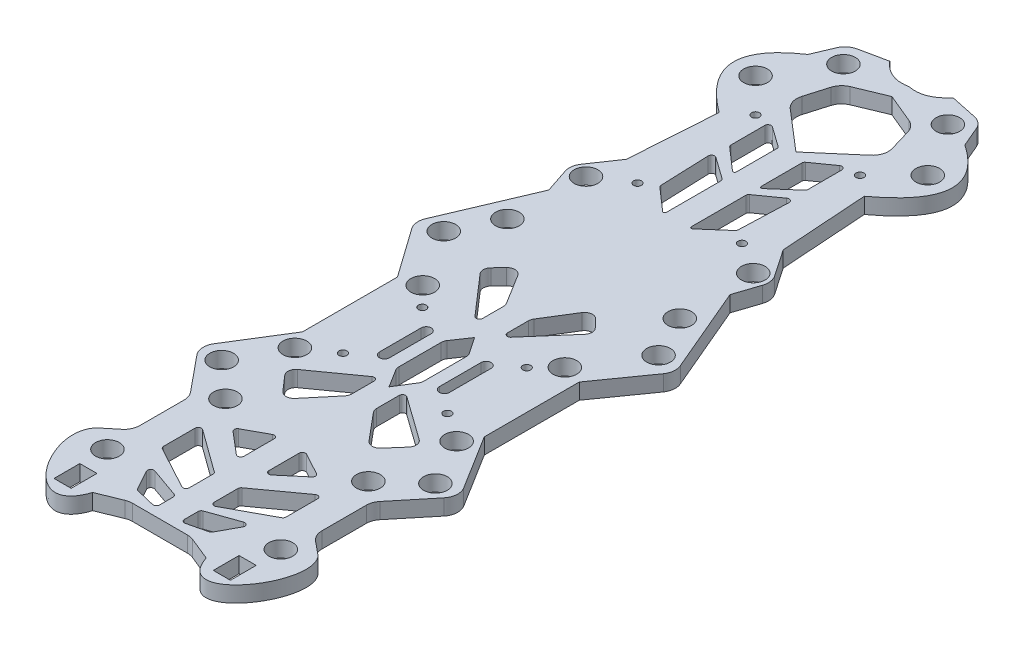
SolidWorks part; units mm, degrees
ref_plane "Front Plane" through (0, 0, 0) normal (0, 0, 1) x (1, 0, 0)
ref_plane "Top Plane" through (0, 0, 0) normal (0, 1, 0) x (1, 0, 0)
ref_plane "Right Plane" through (0, 0, 0) normal (1, 0, 0) x (0, 0, -1)
sketch "Sketch1" plane through (0, 0, 0) normal (0, 1, 0) x (1, 0, 0)
  line L0 (0, -362.1427) -> (0, 100.8573) construction
  line L1 (-20, 108.6669) -> (-37.0216, 105.0994)
  line L2 (-44.1736, 99.2235) -> (-49.5631, 86.5422)
  line L3 (-45.8473, 26.7499) -> (-49.5631, -28.2501)
  line L4 (-49.5631, -28.2501) -> (-61.1711, -45.2719)
  line L5 (-62.3986, -54.0608) -> (-57.2521, -69.541)
  line L6 (-57.2521, -69.541) -> (-80.4938, -124.2273)
  line L7 (-79.4523, -133.9167) -> (-57.4483, -164.9992)
  line L8 (-57.4483, -164.9992) -> (-57.4483, -224.9992)
  line L9 (-57.4483, -224.9992) -> (-78.8878, -259.4412)
  line L10 (-78.1289, -271.0691) -> (-59.8267, -293.374)
  line L11 (-57.5574, -299.7173) -> (-57.5574, -327.686)
  line L12 (-61.214, -335.4166) -> (-70.1168, -342.7217)
  line L13 (-35.8433, -379.1849) -> (-21.2763, -373.2441)
  line L14 (-17.5, -372.5037) -> (17.5, -372.5037)
  line L15 (0, -362.1427) -> (0, -406.857) construction
  line L16 (35.8433, -379.1849) -> (21.2763, -373.2441)
  line L17 (61.214, -335.4166) -> (70.1168, -342.7217)
  line L18 (57.5574, -299.7173) -> (57.5574, -327.686)
  line L19 (78.1289, -271.0691) -> (59.8267, -293.374)
  line L20 (57.4483, -224.9992) -> (78.8878, -259.4412)
  line L21 (57.4483, -164.9992) -> (57.4483, -224.9992)
  line L22 (79.4523, -133.9167) -> (57.4483, -164.9992)
  line L23 (57.2521, -69.541) -> (80.4938, -124.2273)
  line L24 (62.3986, -54.0608) -> (57.2521, -69.541)
  line L25 (49.5631, -28.2501) -> (61.1711, -45.2719)
  line L26 (45.8473, 26.7499) -> (49.5631, -28.2501)
  line L27 (44.1736, 99.2235) -> (49.5631, 86.5422)
  line L28 (20, 108.6669) -> (37.0216, 105.0994)
  line L29 (-82.7668, -406.857) -> (-82.7668, 285.8129) construction
  line L30 (-88.9889, 108.6669) -> (83.0349, 108.6669) construction
  line L31 (83.0349, 108.6669) -> (83.0349, -390.8771) construction
  line L32 (83.0349, -390.8771) -> (-226.8519, -390.8771) construction
  arc A0 (-17.5, -372.5037) -> (-21.2763, -373.2441) centre (-17.5, -382.5037) ccw
  arc A1 (-78.8878, -259.4412) -> (-78.1289, -271.0691) centre (-70.3983, -264.7258) ccw
  arc A2 (-80.4938, -124.2273) -> (-79.4523, -133.9167) centre (-71.2905, -128.1387) ccw
  arc A3 (-61.1711, -45.2719) -> (-62.3986, -54.0608) centre (-52.9093, -50.906) ccw
  arc A4 (-57.5574, -327.686) -> (-61.214, -335.4166) centre (-67.5574, -327.686) cw
  arc A5 (-57.5574, -299.7173) -> (-59.8267, -293.374) centre (-67.5574, -299.7173) ccw
  arc A6 (-44.1736, 99.2235) -> (-37.0216, 105.0994) centre (-34.9703, 95.3121) cw
  arc A7 (44.1736, 99.2235) -> (37.0216, 105.0994) centre (34.9703, 95.3121) ccw
  arc A8 (57.5574, -299.7173) -> (59.8267, -293.374) centre (67.5574, -299.7173) cw
  arc A9 (57.5574, -327.686) -> (61.214, -335.4166) centre (67.5574, -327.686) ccw
  arc A10 (61.1711, -45.2719) -> (62.3986, -54.0608) centre (52.9093, -50.906) cw
  arc A11 (80.4938, -124.2273) -> (79.4523, -133.9167) centre (71.2905, -128.1387) cw
  arc A12 (78.8878, -259.4412) -> (78.1289, -271.0691) centre (70.3983, -264.7258) cw
  arc A13 (17.5, -372.5037) -> (21.2763, -373.2441) centre (17.5, -382.5037) cw
  spline S0 degree 2 poles (0, 100.8573) (-11.4436, 98.5058) (-20, 108.6669) knots 0 0 0 1 1 1
  spline S1 degree 2 poles (-49.5631, 86.5422) (-90.2617, 59.181) (-45.8473, 26.7499) knots 0 0 0 1 1 1
  spline S2 degree 3 poles (-70.1168, -342.7217) (-85.3808, -360.6179) (-47.7027, -414.7904) (-35.8433, -379.1849) knots 0 0 0 0 1 1 1 1
  spline S3 degree 3 poles (70.1168, -342.7217) (85.3808, -360.6179) (47.7027, -414.7904) (35.8433, -379.1849) knots 0 0 0 0 1 1 1 1
  spline S4 degree 2 poles (49.5631, 86.5422) (90.2617, 59.181) (45.8473, 26.7499) knots 0 0 0 1 1 1
  spline S5 degree 2 poles (0, 100.8573) (11.4436, 98.5058) (20, 108.6669) knots 0 0 0 1 1 1
  point P28 (-82.6763, -129.3625)
  point P40 (-42.1315, 104.0285)
  point P74 (0, -372.5037)
  point P78 (42.1315, 104.0285)
  point P81 (81.2332, -129.2074)
  dimension "D2" = 60
  dimension "D3" = 19
  dimension "D4" = 65
  dimension "D6" = 10
  dimension "D7" = 10
  dimension "D8" = 10
  dimension "D9" = 10
  dimension "D10" = 10
  dimension "D11" = 10
  dimension "D12" = 10
  dimension "D5" = 55
  dimension "D13" = 40
  dimension "D14" = 35
  dimension "D15" = 499.544
  dimension "D16" = 165.8017
extrude "Boss-Extrude1" add sketch "Sketch1" along normal blind 10
sketch "Sketch2" plane through (0, 10, 0) normal (0, 1, 0) x (1, 0, 0)
  line L0 (0, 173.7032) -> (0, -467.5162) construction
  line L1 (0, 173.7032) -> (-7.8747, 173.7032) construction
  line L2 (0, 90.0147) -> (-18.6138, 82.2586)
  line L3 (-24.3598, 75.8542) -> (-28.5453, 61.6491)
  line L4 (-25.4693, 51.2374) -> (0, 29.3578)
  line L5 (-7.8747, 173.7032) -> (-7.8747, -465.9658) construction
  line L6 (-8.7157, 26.8032) -> (-21.2008, 35.6817)
  line L7 (-24.3598, 34.0518) -> (-24.3598, 12.6844)
  line L8 (-23.677, 11.1794) -> (-9.5333, -1.1996)
  line L9 (-7.8747, -0.4471) -> (-7.8747, 25.1733)
  line L10 (-8.7157, -8.572) -> (-22.3927, 1.1541)
  line L11 (-25.5504, -0.5507) -> (-24.3921, -31.4898)
  line L12 (-23.7107, -32.92) -> (-9.5333, -45.3284)
  line L13 (-7.8747, -44.5759) -> (-7.8747, -10.2019)
  line L14 (-28.1467, -125.3281) -> (-32.9558, -130.3865)
  line L15 (-33.1054, -137.1123) -> (-11.384, -162.0951)
  line L16 (-7.8747, -160.7828) -> (-7.8747, -147.5558)
  line L17 (-8.6255, -144.9206) -> (-20.2738, -126.138)
  line L18 (0, -173.7386) -> (-7.0144, -184.0936)
  line L19 (-7.8747, -186.8978) -> (-7.8747, -213.6766)
  line L20 (-7.1239, -216.3118) -> (0, -227.7989)
  line L21 (-18.953, -185.3637) -> (-18.953, -211.6699) construction
  line L24 (-15.7584, -185.3637) -> (-15.7584, -211.6699)
  line L25 (-22.1476, -185.3637) -> (-22.1476, -211.6699)
  line L26 (-7.8747, -229.1737) -> (-7.8747, -243.4693)
  line L27 (-9.0405, -246.6785) -> (-23.377, -263.8075)
  line L28 (-30.9765, -263.8881) -> (-39.2293, -254.4426)
  line L29 (-38.3716, -247.0851) -> (-11.0378, -227.5466)
  line L30 (-10.8337, -290.6718) -> (-24.5718, -298.1783)
  line L31 (-24.9054, -301.4595) -> (-11.1673, -313.0946)
  line L32 (-7.8747, -311.5684) -> (-7.8747, -292.4269)
  line L33 (-35.5342, -310.0309) -> (-8.7007, -329.4873)
  line L34 (-7.8747, -331.1065) -> (-7.8747, -346.0976)
  line L35 (-10.8266, -347.8565) -> (-37.66, -333.3358)
  line L36 (-38.7082, -331.5768) -> (-38.7082, -311.65)
  line L37 (-10.3394, -366.8465) -> (-22.4271, -363.9593)
  line L38 (-23.7176, -362.973) -> (-30.4958, -350.5676)
  line L39 (-28.0739, -347.7231) -> (-9.2079, -354.395)
  line L40 (-7.8747, -356.2806) -> (-7.8747, -364.9012)
  line L41 (7.1239, -216.3118) -> (0, -227.7989)
  line L42 (-55.7325, -367.4351) -> (-44.9064, -367.4351)
  line L43 (-55.7325, -367.4351) -> (-55.7325, -383.7424)
  line L44 (-55.7325, -383.7424) -> (-44.9064, -383.7424)
  line L45 (-44.9064, -367.4351) -> (-44.9064, -383.7424)
  line L46 (0, -173.7386) -> (7.0144, -184.0936)
  line L47 (25.4693, 51.2374) -> (0, 29.3578)
  line L48 (0, 90.0147) -> (18.6138, 82.2586)
  line L49 (18.953, -185.3637) -> (18.953, -211.6699) construction
  line L50 (15.7584, -185.3637) -> (15.7584, -211.6699)
  line L51 (22.1476, -185.3637) -> (22.1476, -211.6699)
  line L52 (44.9064, -367.4351) -> (44.9064, -383.7424)
  line L53 (55.7325, -383.7424) -> (44.9064, -383.7424)
  line L54 (55.7325, -367.4351) -> (55.7325, -383.7424)
  line L55 (55.7325, -367.4351) -> (44.9064, -367.4351)
  line L56 (7.8747, -356.2806) -> (7.8747, -364.9012)
  line L57 (28.0739, -347.7231) -> (9.2079, -354.395)
  line L58 (23.7176, -362.973) -> (30.4958, -350.5676)
  line L59 (10.3394, -366.8465) -> (22.4271, -363.9593)
  line L60 (38.7082, -331.5768) -> (38.7082, -311.65)
  line L61 (10.8266, -347.8565) -> (37.66, -333.3358)
  line L62 (7.8747, -331.1065) -> (7.8747, -346.0976)
  line L63 (35.5342, -310.0309) -> (8.7007, -329.4873)
  line L64 (7.8747, -311.5684) -> (7.8747, -292.4269)
  line L65 (24.9054, -301.4595) -> (11.1673, -313.0946)
  line L66 (10.8337, -290.6718) -> (24.5718, -298.1783)
  line L67 (38.3716, -247.0851) -> (11.0378, -227.5466)
  line L68 (30.9765, -263.8881) -> (39.2293, -254.4426)
  line L69 (9.0405, -246.6785) -> (23.377, -263.8075)
  line L70 (7.8747, -229.1737) -> (7.8747, -243.4693)
  line L71 (7.8747, -186.8978) -> (7.8747, -213.6766)
  line L72 (8.6255, -144.9206) -> (20.2738, -126.138)
  line L73 (7.8747, -160.7828) -> (7.8747, -147.5558)
  line L74 (33.1054, -137.1123) -> (11.384, -162.0951)
  line L75 (28.1467, -125.3281) -> (32.9558, -130.3865)
  line L76 (7.8747, -44.5759) -> (7.8747, -10.2019)
  line L77 (23.7107, -32.92) -> (9.5333, -45.3284)
  line L78 (25.5504, -0.5507) -> (24.3921, -31.4898)
  line L79 (8.7157, -8.572) -> (22.3927, 1.1541)
  line L80 (7.8747, -0.4471) -> (7.8747, 25.1733)
  line L81 (23.677, 11.1794) -> (9.5333, -1.1996)
  line L82 (24.3598, 34.0518) -> (24.3598, 12.6844)
  line L83 (8.7157, 26.8032) -> (21.2008, 35.6817)
  line L84 (24.3598, 75.8542) -> (28.5453, 61.6491)
  circle A0 centre (-33.0024, 92.3922) radius 7.5
  circle A1 centre (-54.4295, 58.2676) radius 7.5
  circle A2 centre (-33.0024, 36.8405) radius 2.5
  circle A3 centre (-33.0024, -37.7574) radius 2.5
  circle A4 centre (-52.8423, -50.455) radius 7.5
  circle A7 centre (-44.9064, -161.5583) radius 7.5
  circle A8 centre (-51.1045, -236.1562) radius 7.5
  circle A9 centre (-67.5328, -265.9713) radius 7.5
  circle A10 centre (-45.1721, -285.9713) radius 7.5
  circle A12 centre (-33.0024, -173.7386) radius 2.5
  circle A13 centre (-33.0024, -223.892) radius 2.5
  arc A14 (-28.5453, 61.6491) -> (-25.4693, 51.2374) centre (-18.953, 58.8228) ccw
  arc A15 (-24.3598, 75.8542) -> (-18.6138, 82.2586) centre (-14.7675, 73.0279) cw
  arc A16 (-21.2008, 35.6817) -> (-24.3598, 34.0518) centre (-22.3598, 34.0518) ccw
  arc A17 (-7.8747, 25.1733) -> (-8.7157, 26.8032) centre (-9.8747, 25.1733) ccw
  arc A18 (-23.677, 11.1794) -> (-24.3598, 12.6844) centre (-22.3598, 12.6844) cw
  arc A19 (-22.3927, 1.1541) -> (-25.5504, -0.5507) centre (-23.5518, -0.4758) ccw
  arc A20 (-24.3921, -31.4898) -> (-23.7107, -32.92) centre (-22.3935, -31.415) ccw
  arc A21 (-7.8747, -10.2019) -> (-8.7157, -8.572) centre (-9.8747, -10.2019) ccw
  arc A22 (-7.8747, -0.4471) -> (-9.5333, -1.1996) centre (-8.8747, -0.4471) cw
  arc A23 (-7.8747, -44.5759) -> (-9.5333, -45.3284) centre (-8.8747, -44.5759) cw
  arc A26 (-15.7584, -185.3637) -> (-22.1476, -185.3637) centre (-18.953, -185.3637) ccw
  arc A27 (-22.1476, -211.6699) -> (-15.7584, -211.6699) centre (-18.953, -211.6699) ccw
  arc A28 (-20.2738, -126.138) -> (-28.1467, -125.3281) centre (-24.523, -128.7732) ccw
  arc A29 (-32.9558, -130.3865) -> (-33.1054, -137.1123) centre (-29.3321, -133.8316) ccw
  arc A30 (-7.8747, -147.5558) -> (-8.6255, -144.9206) centre (-12.8747, -147.5558) ccw
  arc A31 (-7.8747, -160.7828) -> (-11.384, -162.0951) centre (-9.8747, -160.7828) cw
  arc A32 (-7.8747, -229.1737) -> (-11.0378, -227.5466) centre (-9.8747, -229.1737) ccw
  arc A33 (-7.8747, -243.4693) -> (-9.0405, -246.6785) centre (-12.8747, -243.4693) cw
  arc A34 (-38.3716, -247.0851) -> (-39.2293, -254.4426) centre (-35.464, -251.1528) ccw
  arc A35 (-23.377, -263.8075) -> (-30.9765, -263.8881) centre (-27.2113, -260.5983) cw
  arc A36 (-24.9054, -301.4595) -> (-24.5718, -298.1783) centre (-23.6129, -299.9334) cw
  arc A37 (-7.8747, -292.4269) -> (-10.8337, -290.6718) centre (-9.8747, -292.4269) ccw
  arc A38 (-7.8747, -311.5684) -> (-11.1673, -313.0946) centre (-9.8747, -311.5684) cw
  arc A39 (-35.5342, -310.0309) -> (-38.7082, -311.65) centre (-36.7082, -311.65) ccw
  arc A40 (-7.8747, -331.1065) -> (-8.7007, -329.4873) centre (-9.8747, -331.1065) ccw
  arc A41 (-7.8747, -346.0976) -> (-10.8266, -347.8565) centre (-9.8747, -346.0976) cw
  arc A42 (-38.7082, -331.5768) -> (-37.66, -333.3358) centre (-36.7082, -331.5768) ccw
  arc A43 (-28.0739, -347.7231) -> (-30.4958, -350.5676) centre (-28.7407, -349.6086) ccw
  arc A44 (-7.8747, -364.9012) -> (-10.3394, -366.8465) centre (-9.8747, -364.9012) cw
  arc A45 (-22.4271, -363.9593) -> (-23.7176, -362.973) centre (-21.9625, -362.014) cw
  arc A46 (-7.8747, -356.2806) -> (-9.2079, -354.395) centre (-9.8747, -356.2806) ccw
  arc A47 (-7.0144, -184.0936) -> (-7.8747, -186.8978) centre (-2.8747, -186.8978) ccw
  arc A48 (-7.8747, -213.6766) -> (-7.1239, -216.3118) centre (-2.8747, -213.6766) ccw
  arc A49 (15.7584, -185.3637) -> (22.1476, -185.3637) centre (18.953, -185.3637) cw
  arc A50 (22.1476, -211.6699) -> (15.7584, -211.6699) centre (18.953, -211.6699) cw
  arc A51 (7.8747, -213.6766) -> (7.1239, -216.3118) centre (2.8747, -213.6766) cw
  arc A52 (7.0144, -184.0936) -> (7.8747, -186.8978) centre (2.8747, -186.8978) cw
  arc A53 (7.8747, -356.2806) -> (9.2079, -354.395) centre (9.8747, -356.2806) cw
  arc A54 (22.4271, -363.9593) -> (23.7176, -362.973) centre (21.9625, -362.014) ccw
  arc A55 (7.8747, -364.9012) -> (10.3394, -366.8465) centre (9.8747, -364.9012) ccw
  arc A56 (28.0739, -347.7231) -> (30.4958, -350.5676) centre (28.7407, -349.6086) cw
  arc A57 (38.7082, -331.5768) -> (37.66, -333.3358) centre (36.7082, -331.5768) cw
  arc A58 (7.8747, -346.0976) -> (10.8266, -347.8565) centre (9.8747, -346.0976) ccw
  arc A59 (7.8747, -331.1065) -> (8.7007, -329.4873) centre (9.8747, -331.1065) cw
  arc A60 (35.5342, -310.0309) -> (38.7082, -311.65) centre (36.7082, -311.65) cw
  arc A61 (7.8747, -311.5684) -> (11.1673, -313.0946) centre (9.8747, -311.5684) ccw
  arc A62 (7.8747, -292.4269) -> (10.8337, -290.6718) centre (9.8747, -292.4269) cw
  arc A63 (24.9054, -301.4595) -> (24.5718, -298.1783) centre (23.6129, -299.9334) ccw
  arc A64 (23.377, -263.8075) -> (30.9765, -263.8881) centre (27.2113, -260.5983) ccw
  arc A65 (38.3716, -247.0851) -> (39.2293, -254.4426) centre (35.464, -251.1528) cw
  arc A66 (7.8747, -243.4693) -> (9.0405, -246.6785) centre (12.8747, -243.4693) ccw
  arc A67 (7.8747, -229.1737) -> (11.0378, -227.5466) centre (9.8747, -229.1737) cw
  arc A68 (7.8747, -160.7828) -> (11.384, -162.0951) centre (9.8747, -160.7828) ccw
  arc A69 (7.8747, -147.5558) -> (8.6255, -144.9206) centre (12.8747, -147.5558) cw
  arc A70 (32.9558, -130.3865) -> (33.1054, -137.1123) centre (29.3321, -133.8316) cw
  arc A71 (20.2738, -126.138) -> (28.1467, -125.3281) centre (24.523, -128.7732) cw
  arc A72 (7.8747, -44.5759) -> (9.5333, -45.3284) centre (8.8747, -44.5759) ccw
  arc A73 (7.8747, -0.4471) -> (9.5333, -1.1996) centre (8.8747, -0.4471) ccw
  arc A74 (7.8747, -10.2019) -> (8.7157, -8.572) centre (9.8747, -10.2019) cw
  arc A75 (24.3921, -31.4898) -> (23.7107, -32.92) centre (22.3935, -31.415) cw
  arc A76 (22.3927, 1.1541) -> (25.5504, -0.5507) centre (23.5518, -0.4758) cw
  arc A77 (23.677, 11.1794) -> (24.3598, 12.6844) centre (22.3598, 12.6844) ccw
  arc A78 (7.8747, 25.1733) -> (8.7157, 26.8032) centre (9.8747, 25.1733) cw
  arc A79 (21.2008, 35.6817) -> (24.3598, 34.0518) centre (22.3598, 34.0518) cw
  arc A80 (24.3598, 75.8542) -> (18.6138, 82.2586) centre (14.7675, 73.0279) ccw
  arc A81 (28.5453, 61.6491) -> (25.4693, 51.2374) centre (18.953, 58.8228) cw
  circle A82 centre (33.0024, -223.892) radius 2.5
  circle A83 centre (33.0024, -173.7386) radius 2.5
  circle A85 centre (45.1721, -285.9713) radius 7.5
  circle A86 centre (67.5328, -265.9713) radius 7.5
  circle A87 centre (51.1045, -236.1562) radius 7.5
  circle A88 centre (44.9064, -161.5583) radius 7.5
  circle A91 centre (52.8423, -50.455) radius 7.5
  circle A92 centre (33.0024, -37.7574) radius 2.5
  circle A93 centre (33.0024, 36.8405) radius 2.5
  circle A94 centre (54.4295, 58.2676) radius 7.5
  circle A95 centre (33.0024, 92.3922) radius 7.5
  circle A96 centre (-54.7734, -350.9288) radius 7.5
  circle A97 centre (54.7734, -350.9288) radius 7.5
  circle A98 centre (-67.8872, -125.3281) radius 7.5
  circle A99 centre (-54.4686, -98.4964) radius 7.5
  circle A100 centre (54.4686, -98.4964) radius 7.5
  circle A101 centre (67.8872, -125.3281) radius 7.5
  point P40 (-13.7481, 98.3364)
  point P54 (-7.8747, 26.2052)
  point P63 (-7.8747, -9.17)
  point P66 (-7.8747, -2.6512)
  point P69 (-7.8747, -46.7801)
  point P80 (-18.953, -198.5168)
  point P107 (-23.686, -120.6361)
  point P110 (-36.0883, -133.6814)
  point P113 (-7.8747, -146.1313)
  point P116 (-7.8747, -166.1313)
  point P119 (-7.8747, -225.2856)
  point P122 (-7.8747, -245.2856)
  point P125 (-42.8566, -250.291)
  point P128 (-27.1296, -268.291)
  point P133 (-7.8747, -289.055)
  point P136 (-7.8747, -315.8831)
  point P141 (-7.8747, -330.0862)
  point P144 (-7.8747, -349.4539)
  point P151 (-7.8747, -367.4351)
  point P156 (-7.8747, -354.8665)
  point P159 (-7.8747, -185.3637)
  point P162 (-7.8747, -215.1011)
  point P169 (18.953, -198.5168)
  point P295 (7.8747, -215.1011)
  point P296 (7.8747, -185.3637)
  point P297 (7.8747, -354.8665)
  point P298 (7.8747, -367.4351)
  point P299 (7.8747, -349.4539)
  point P300 (7.8747, -330.0862)
  point P301 (7.8747, -315.8831)
  point P302 (7.8747, -289.055)
  point P303 (27.1296, -268.291)
  point P304 (42.8566, -250.291)
  point P305 (7.8747, -245.2856)
  point P306 (7.8747, -225.2856)
  point P307 (7.8747, -166.1313)
  point P308 (7.8747, -146.1313)
  point P309 (36.0883, -133.6814)
  point P310 (23.686, -120.6361)
  point P311 (7.8747, -46.7801)
  point P312 (7.8747, -2.6512)
  point P313 (7.8747, -9.17)
  point P314 (7.8747, 26.2052)
  point P315 (13.7481, 98.3364)
  dimension "D1" = 15
  dimension "D2" = 15
  dimension "D3" = 5
  dimension "D4" = 5
  dimension "D5" = 15
  dimension "D6" = 15
  dimension "D7" = 15
  dimension "D8" = 15
  dimension "D9" = 15
  dimension "D10" = 15
  dimension "D11" = 15
  dimension "D12" = 15
  dimension "D13" = 5
  dimension "D14" = 5
  dimension "D15" = 10
  dimension "D16" = 10
  dimension "D17" = 2
  dimension "D18" = 2
  dimension "D19" = 2
  dimension "D20" = 2
  dimension "D21" = 2
  dimension "D22" = 2
  dimension "D23" = 1
  dimension "D24" = 1
  dimension "D33" = 5
  dimension "D34" = 5
  dimension "D35" = 5
  dimension "D36" = 2
  dimension "D37" = 2
  dimension "D38" = 5
  dimension "D39" = 5
  dimension "D40" = 5
  dimension "D41" = 2
  dimension "D42" = 2
  dimension "D43" = 2
  dimension "D44" = 2
  dimension "D45" = 2
  dimension "D46" = 2
  dimension "D47" = 2
  dimension "D48" = 2
  dimension "D49" = 2
  dimension "D50" = 2
  dimension "D51" = 2
  dimension "D52" = 5
  dimension "D53" = 5
  dimension "D54" = 20
  dimension "D55" = 30
  dimension "D25" = 20
  dimension "D26" = 18
  dimension "D27" = 30
  dimension "D28" = 43
  dimension "D29" = 43
  dimension "D30" = 30
  dimension "D31" = 18
  dimension "D32" = 20
  dimension "D56" = 30
extrude "Cut-Extrude1" cut sketch "Sketch2" against normal blind 10
scale "Scale1" scale about centroid uniform scaling yes scale factor 0.5
